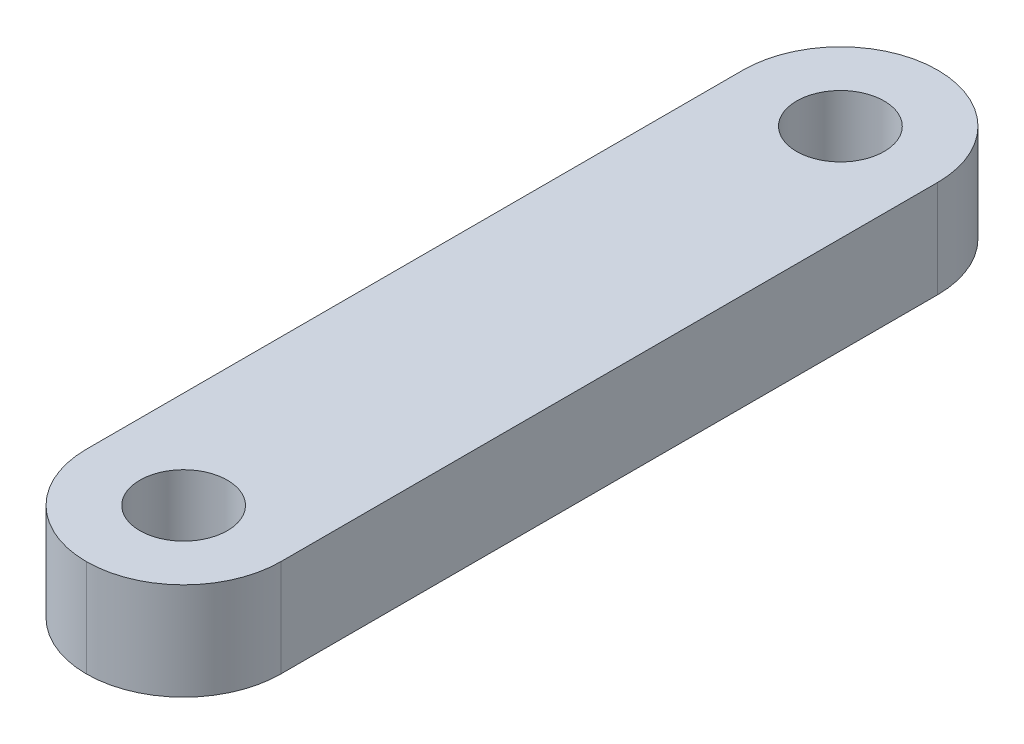
SolidWorks part; units mm, degrees
ref_plane "Front" through (0, 0, 0) normal (0, 0, 1) x (1, 0, 0)
ref_plane "Top" through (0, 0, 0) normal (0, 1, 0) x (1, 0, 0)
ref_plane "Right" through (0, 0, 0) normal (1, 0, 0) x (0, 0, -1)
sketch "Sketch1" plane through (0, 0, 0) normal (0, 0, 1) x (1, 0, 0)
  line L1 (0, 0) -> (8, 0)
  line L2 (0, 0) -> (0, -4)
  line L3 (0, -4) -> (8, -4)
  line L4 (8, 0) -> (8, -4)
  dimension "D1" = 4
  dimension "D2" = 8
extrude "Boss-Extrude1" add sketch "Sketch1" along normal blind 35
sketch "Sketch2" plane through (0, 0, 0) normal (0, 1, 0) x (1, 0, 0)
  line L0 (8, -35) -> (0, -35) construction
  line L1 (8, -35) -> (8, 0) construction
  line L2 (8, 0) -> (0, 0) construction
  circle A0 centre (4, -4) radius 1.8
  circle A1 centre (4, -31) radius 1.8
  dimension "D1" = 3.6
  dimension "D2" = 3.6
  dimension "D3" = 4
  dimension "D4" = 4
  dimension "D5" = 4
  dimension "D6" = 4
extrude "Cut-Extrude1" cut sketch "Sketch2" against normal through all
fillet "Fillet1" radius 4 4 edges at (0, -2, 0) (8, -2, 0) (0, -2, 35) (8, -2, 35)
equation "\"滑动-垂直孔\" = 0.6"
equation "\"滑动-水平孔\"= 0.3"
equation "\"松动-垂直孔\" = 0.3"
equation "\"松动-水平孔\"= 0.1"
equation "\"正常-垂直孔\" = 0.15"
equation "\"正常-水平孔\"= 0"
equation "\"紧缩-垂直孔\"= 0"
equation "\"紧缩-水平孔\"= - 0.1"
equation "\"D1@Sketch2\"=\"滑动-垂直孔\"+3"
equation "\"D2@Sketch2\"=\"滑动-垂直孔\"+3"
